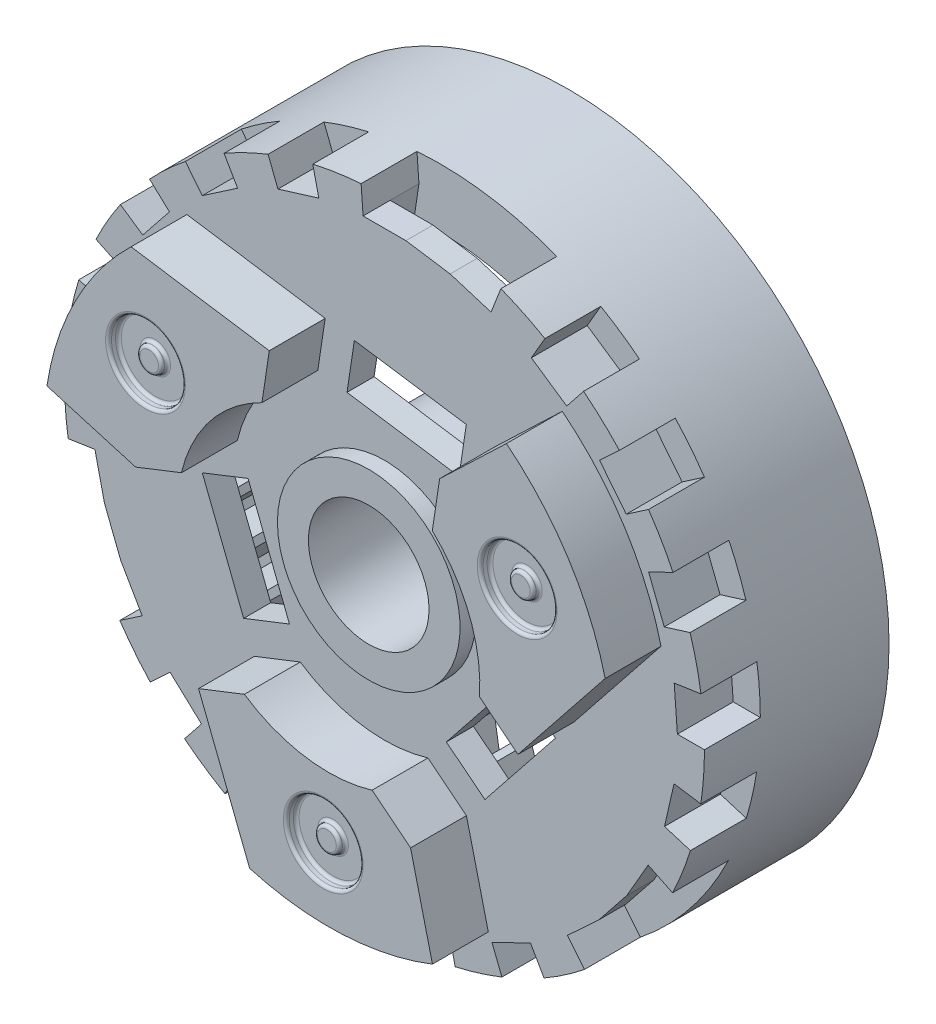
SolidWorks part; units mm, degrees
ref_plane "Front Plane" through (0, 0, 0) normal (0, 0, 1) x (1, 0, 0)
ref_plane "Top Plane" through (0, 0, 0) normal (0, 1, 0) x (1, 0, 0)
ref_plane "Right Plane" through (0, 0, 0) normal (1, 0, 0) x (0, 0, -1)
sketch "Sketch1" plane through (0, 0, 0) normal (0, 0, 1) x (1, 0, 0)
  circle A0 centre (0, 0) radius 13
  circle A1 centre (0, 0) radius 10.6
  dimension "D1" = 26
  dimension "D2" = 2.4
extrude "Boss-Extrude1" add sketch "Sketch1" along normal blind 7.5 contours A0 A1 | A1 region at (-12.6323, 0, 0) region at (0, 0, 0)
extrude "Cut-Extrude1" cut sketch "Sketch1<3>" along normal blind 6.4 contours A1
sketch "Sketch1<3>" plane through (0, 0, 0) normal (0, 0, 1) x (1, 0, 0) same geometry as "Sketch1"
sketch "Sketch2" plane through (0, 0, 0) normal (0, 0, -1) x (-1, 0, 0)
  line L0 (1.5404, 10.7139) -> (2.2569, 11.7861)
  line L1 (0, 10.8241) -> (0.5566, 11.9874)
  line L2 (0.5566, 11.9874) -> (0.8558, 11.966)
  line L3 (0.8558, 11.966) -> (1.2412, 10.7353)
  line L4 (1.2412, 10.7353) -> (1.5404, 10.7139)
  line L5 (0, 10.8241) -> (1.2412, 10.7353) construction
  line L6 (0.7062, 11.9767) -> (0.6206, 10.7797) construction
  line L7 (2.2569, 11.7861) -> (2.55, 11.7224)
  line L8 (2.55, 11.7224) -> (2.7564, 10.4494)
  line L9 (2.7564, 10.4494) -> (3.0495, 10.3857)
  line L10 (1.5404, 10.7139) -> (2.7564, 10.4494) construction
  line L11 (2.4035, 11.7543) -> (2.1484, 10.5817) construction
  line L12 (3.0495, 10.3857) -> (3.9113, 11.345)
  line L13 (3.9113, 11.345) -> (4.1924, 11.2402)
  line L14 (4.1924, 11.2402) -> (4.2154, 9.9508)
  line L15 (4.2154, 9.9508) -> (4.4965, 9.846)
  line L16 (3.0495, 10.3857) -> (4.2154, 9.9508) construction
  line L17 (4.0518, 11.2926) -> (3.6325, 10.1682) construction
  line L18 (4.4965, 9.846) -> (5.486, 10.6729)
  line L19 (5.486, 10.6729) -> (5.7493, 10.5291)
  line L20 (5.7493, 10.5291) -> (5.5887, 9.2496)
  line L21 (5.5887, 9.2496) -> (5.852, 9.1058)
  line L22 (4.4965, 9.846) -> (5.5887, 9.2496) construction
  line L23 (5.6177, 10.601) -> (5.0426, 9.5478) construction
  line L24 (5.852, 9.1058) -> (6.9491, 9.7835)
  line L25 (6.9491, 9.7835) -> (7.1893, 9.6037)
  line L26 (7.1893, 9.6037) -> (6.8481, 8.3601)
  line L27 (6.8481, 8.3601) -> (7.0883, 8.1803)
  line L28 (5.852, 9.1058) -> (6.8481, 8.3601) construction
  line L29 (7.0692, 9.6936) -> (6.35, 8.733) construction
  line L30 (7.0883, 8.1803) -> (8.2707, 8.695)
  line L31 (8.2707, 8.695) -> (8.4828, 8.4828)
  line L32 (8.4828, 8.4828) -> (7.9682, 7.3004)
  line L33 (7.9682, 7.3004) -> (8.1803, 7.0883)
  line L34 (7.0883, 8.1803) -> (7.9682, 7.3004) construction
  line L35 (8.3768, 8.5889) -> (7.5282, 7.7404) construction
  line L36 (8.1803, 7.0883) -> (9.4239, 7.4294)
  line L37 (9.4239, 7.4294) -> (9.6037, 7.1893)
  line L38 (9.6037, 7.1893) -> (8.926, 6.0921)
  line L39 (8.926, 6.0921) -> (9.1058, 5.852)
  line L40 (8.1803, 7.0883) -> (8.926, 6.0921) construction
  line L41 (9.5138, 7.3093) -> (8.5532, 6.5902) construction
  line L42 (9.1058, 5.852) -> (10.3853, 6.0126)
  line L43 (10.3853, 6.0126) -> (10.5291, 5.7493)
  line L44 (10.5291, 5.7493) -> (9.7022, 4.7598)
  line L45 (9.7022, 4.7598) -> (9.846, 4.4965)
  line L46 (9.1058, 5.852) -> (9.7022, 4.7598) construction
  line L47 (10.4572, 5.881) -> (9.404, 5.3059) construction
  line L48 (9.846, 4.4965) -> (11.1353, 4.4734)
  line L49 (11.1353, 4.4734) -> (11.2402, 4.1924)
  line L50 (11.2402, 4.1924) -> (10.2808, 3.3306)
  line L51 (10.2808, 3.3306) -> (10.3857, 3.0495)
  line L52 (9.846, 4.4965) -> (10.2808, 3.3306) construction
  line L53 (11.1877, 4.3329) -> (10.0634, 3.9135) construction
  line L54 (10.3857, 3.0495) -> (11.6586, 2.8432)
  line L55 (11.6586, 2.8432) -> (11.7224, 2.55)
  line L56 (11.7224, 2.55) -> (10.6502, 1.8336)
  line L57 (10.6502, 1.8336) -> (10.7139, 1.5404)
  line L58 (10.3857, 3.0495) -> (10.6502, 1.8336) construction
  line L59 (11.6905, 2.6966) -> (10.5179, 2.4415) construction
  line L60 (10.7139, 1.5404) -> (11.9446, 1.1551)
  line L61 (11.9446, 1.1551) -> (11.966, 0.8558)
  line L62 (11.966, 0.8558) -> (10.8027, 0.2992)
  line L63 (10.8027, 0.2992) -> (10.8241, 0)
  line L64 (10.7139, 1.5404) -> (10.8027, 0.2992) construction
  line L65 (11.9553, 1.0054) -> (10.7583, 0.9198) construction
  line L66 (10.8241, 0) -> (11.9874, -0.5566)
  line L67 (11.9874, -0.5566) -> (11.966, -0.8558)
  line L68 (11.966, -0.8558) -> (10.7353, -1.2412)
  line L69 (10.7353, -1.2412) -> (10.7139, -1.5404)
  line L70 (10.8241, 0) -> (10.7353, -1.2412) construction
  line L71 (11.9767, -0.7062) -> (10.7797, -0.6206) construction
  line L72 (10.7139, -1.5404) -> (11.7861, -2.2569)
  line L73 (11.7861, -2.2569) -> (11.7224, -2.55)
  line L74 (11.7224, -2.55) -> (10.4494, -2.7564)
  line L75 (10.4494, -2.7564) -> (10.3857, -3.0495)
  line L76 (10.7139, -1.5404) -> (10.4494, -2.7564) construction
  line L77 (11.7543, -2.4035) -> (10.5817, -2.1484) construction
  line L78 (10.3857, -3.0495) -> (11.345, -3.9113)
  line L79 (11.345, -3.9113) -> (11.2402, -4.1924)
  line L80 (11.2402, -4.1924) -> (9.9508, -4.2154)
  line L81 (9.9508, -4.2154) -> (9.846, -4.4965)
  line L82 (10.3857, -3.0495) -> (9.9508, -4.2154) construction
  line L83 (11.2926, -4.0518) -> (10.1682, -3.6325) construction
  line L84 (9.846, -4.4965) -> (10.6729, -5.486)
  line L85 (10.6729, -5.486) -> (10.5291, -5.7493)
  line L86 (10.5291, -5.7493) -> (9.2496, -5.5887)
  line L87 (9.2496, -5.5887) -> (9.1058, -5.852)
  line L88 (9.846, -4.4965) -> (9.2496, -5.5887) construction
  line L89 (10.601, -5.6177) -> (9.5478, -5.0426) construction
  line L90 (9.1058, -5.852) -> (9.7835, -6.9491)
  line L91 (9.7835, -6.9491) -> (9.6037, -7.1893)
  line L92 (9.6037, -7.1893) -> (8.3601, -6.8481)
  line L93 (8.3601, -6.8481) -> (8.1803, -7.0883)
  line L94 (9.1058, -5.852) -> (8.3601, -6.8481) construction
  line L95 (9.6936, -7.0692) -> (8.733, -6.35) construction
  line L96 (8.1803, -7.0883) -> (8.695, -8.2707)
  line L97 (8.695, -8.2707) -> (8.4828, -8.4828)
  line L98 (8.4828, -8.4828) -> (7.3004, -7.9682)
  line L99 (7.3004, -7.9682) -> (7.0883, -8.1803)
  line L100 (8.1803, -7.0883) -> (7.3004, -7.9682) construction
  line L101 (8.5889, -8.3768) -> (7.7404, -7.5282) construction
  line L102 (7.0883, -8.1803) -> (7.4294, -9.4239)
  line L103 (7.4294, -9.4239) -> (7.1893, -9.6037)
  line L104 (7.1893, -9.6037) -> (6.0921, -8.926)
  line L105 (6.0921, -8.926) -> (5.852, -9.1058)
  line L106 (7.0883, -8.1803) -> (6.0921, -8.926) construction
  line L107 (7.3093, -9.5138) -> (6.5902, -8.5532) construction
  line L108 (5.852, -9.1058) -> (6.0126, -10.3853)
  line L109 (6.0126, -10.3853) -> (5.7493, -10.5291)
  line L110 (5.7493, -10.5291) -> (4.7598, -9.7022)
  line L111 (4.7598, -9.7022) -> (4.4965, -9.846)
  line L112 (5.852, -9.1058) -> (4.7598, -9.7022) construction
  line L113 (5.881, -10.4572) -> (5.3059, -9.404) construction
  line L114 (4.4965, -9.846) -> (4.4734, -11.1353)
  line L115 (4.4734, -11.1353) -> (4.1924, -11.2402)
  line L116 (4.1924, -11.2402) -> (3.3306, -10.2808)
  line L117 (3.3306, -10.2808) -> (3.0495, -10.3857)
  line L118 (4.4965, -9.846) -> (3.3306, -10.2808) construction
  line L119 (4.3329, -11.1877) -> (3.9135, -10.0634) construction
  line L120 (3.0495, -10.3857) -> (2.8432, -11.6586)
  line L121 (2.8432, -11.6586) -> (2.55, -11.7224)
  line L122 (2.55, -11.7224) -> (1.8336, -10.6502)
  line L123 (1.8336, -10.6502) -> (1.5404, -10.7139)
  line L124 (3.0495, -10.3857) -> (1.8336, -10.6502) construction
  line L125 (2.6966, -11.6905) -> (2.4415, -10.5179) construction
  line L126 (1.5404, -10.7139) -> (1.1551, -11.9446)
  line L127 (1.1551, -11.9446) -> (0.8558, -11.966)
  line L128 (0.8558, -11.966) -> (0.2992, -10.8027)
  line L129 (0.2992, -10.8027) -> (0, -10.8241)
  line L130 (1.5404, -10.7139) -> (0.2992, -10.8027) construction
  line L131 (1.0054, -11.9553) -> (0.9198, -10.7583) construction
  line L132 (0, -10.8241) -> (-0.5566, -11.9874)
  line L133 (-0.5566, -11.9874) -> (-0.8558, -11.966)
  line L134 (-0.8558, -11.966) -> (-1.2412, -10.7353)
  line L135 (-1.2412, -10.7353) -> (-1.5404, -10.7139)
  line L136 (0, -10.8241) -> (-1.2412, -10.7353) construction
  line L137 (-0.7062, -11.9767) -> (-0.6206, -10.7797) construction
  line L138 (-1.5404, -10.7139) -> (-2.2569, -11.7861)
  line L139 (-2.2569, -11.7861) -> (-2.55, -11.7224)
  line L140 (-2.55, -11.7224) -> (-2.7564, -10.4494)
  line L141 (-2.7564, -10.4494) -> (-3.0495, -10.3857)
  line L142 (-1.5404, -10.7139) -> (-2.7564, -10.4494) construction
  line L143 (-2.4035, -11.7543) -> (-2.1484, -10.5817) construction
  line L144 (-3.0495, -10.3857) -> (-3.9113, -11.345)
  line L145 (-3.9113, -11.345) -> (-4.1924, -11.2402)
  line L146 (-4.1924, -11.2402) -> (-4.2154, -9.9508)
  line L147 (-4.2154, -9.9508) -> (-4.4965, -9.846)
  line L148 (-3.0495, -10.3857) -> (-4.2154, -9.9508) construction
  line L149 (-4.0518, -11.2926) -> (-3.6325, -10.1682) construction
  line L150 (-4.4965, -9.846) -> (-5.486, -10.6729)
  line L151 (-5.486, -10.6729) -> (-5.7493, -10.5291)
  line L152 (-5.7493, -10.5291) -> (-5.5887, -9.2496)
  line L153 (-5.5887, -9.2496) -> (-5.852, -9.1058)
  line L154 (-4.4965, -9.846) -> (-5.5887, -9.2496) construction
  line L155 (-5.6177, -10.601) -> (-5.0426, -9.5478) construction
  line L156 (-5.852, -9.1058) -> (-6.9491, -9.7835)
  line L157 (-6.9491, -9.7835) -> (-7.1893, -9.6037)
  line L158 (-7.1893, -9.6037) -> (-6.8481, -8.3601)
  line L159 (-6.8481, -8.3601) -> (-7.0883, -8.1803)
  line L160 (-5.852, -9.1058) -> (-6.8481, -8.3601) construction
  line L161 (-7.0692, -9.6936) -> (-6.35, -8.733) construction
  line L162 (-7.0883, -8.1803) -> (-8.2707, -8.695)
  line L163 (-8.2707, -8.695) -> (-8.4828, -8.4828)
  line L164 (-8.4828, -8.4828) -> (-7.9682, -7.3004)
  line L165 (-7.9682, -7.3004) -> (-8.1803, -7.0883)
  line L166 (-7.0883, -8.1803) -> (-7.9682, -7.3004) construction
  line L167 (-8.3768, -8.5889) -> (-7.5282, -7.7404) construction
  line L168 (-8.1803, -7.0883) -> (-9.4239, -7.4294)
  line L169 (-9.4239, -7.4294) -> (-9.6037, -7.1893)
  line L170 (-9.6037, -7.1893) -> (-8.926, -6.0921)
  line L171 (-8.926, -6.0921) -> (-9.1058, -5.852)
  line L172 (-8.1803, -7.0883) -> (-8.926, -6.0921) construction
  line L173 (-9.5138, -7.3093) -> (-8.5532, -6.5902) construction
  line L174 (-9.1058, -5.852) -> (-10.3853, -6.0126)
  line L175 (-10.3853, -6.0126) -> (-10.5291, -5.7493)
  line L176 (-10.5291, -5.7493) -> (-9.7022, -4.7598)
  line L177 (-9.7022, -4.7598) -> (-9.846, -4.4965)
  line L178 (-9.1058, -5.852) -> (-9.7022, -4.7598) construction
  line L179 (-10.4572, -5.881) -> (-9.404, -5.3059) construction
  line L180 (-9.846, -4.4965) -> (-11.1353, -4.4734)
  line L181 (-11.1353, -4.4734) -> (-11.2402, -4.1924)
  line L182 (-11.2402, -4.1924) -> (-10.2808, -3.3306)
  line L183 (-10.2808, -3.3306) -> (-10.3857, -3.0495)
  line L184 (-9.846, -4.4965) -> (-10.2808, -3.3306) construction
  line L185 (-11.1877, -4.3329) -> (-10.0634, -3.9135) construction
  line L186 (-10.3857, -3.0495) -> (-11.6586, -2.8432)
  line L187 (-11.6586, -2.8432) -> (-11.7224, -2.55)
  line L188 (-11.7224, -2.55) -> (-10.6502, -1.8336)
  line L189 (-10.6502, -1.8336) -> (-10.7139, -1.5404)
  line L190 (-10.3857, -3.0495) -> (-10.6502, -1.8336) construction
  line L191 (-11.6905, -2.6966) -> (-10.5179, -2.4415) construction
  line L192 (-10.7139, -1.5404) -> (-11.9446, -1.1551)
  line L193 (-11.9446, -1.1551) -> (-11.966, -0.8558)
  line L194 (-11.966, -0.8558) -> (-10.8027, -0.2992)
  line L195 (-10.8027, -0.2992) -> (-10.8241, 0)
  line L196 (-10.7139, -1.5404) -> (-10.8027, -0.2992) construction
  line L197 (-11.9553, -1.0054) -> (-10.7583, -0.9198) construction
  line L198 (-10.8241, 0) -> (-11.9874, 0.5566)
  line L199 (-11.9874, 0.5566) -> (-11.966, 0.8558)
  line L200 (-11.966, 0.8558) -> (-10.7353, 1.2412)
  line L201 (-10.7353, 1.2412) -> (-10.7139, 1.5404)
  line L202 (-10.8241, 0) -> (-10.7353, 1.2412) construction
  line L203 (-11.9767, 0.7062) -> (-10.7797, 0.6206) construction
  line L204 (-10.7139, 1.5404) -> (-11.7861, 2.2569)
  line L205 (-11.7861, 2.2569) -> (-11.7224, 2.55)
  line L206 (-11.7224, 2.55) -> (-10.4494, 2.7564)
  line L207 (-10.4494, 2.7564) -> (-10.3857, 3.0495)
  line L208 (-10.7139, 1.5404) -> (-10.4494, 2.7564) construction
  line L209 (-11.7543, 2.4035) -> (-10.5817, 2.1484) construction
  line L210 (-10.3857, 3.0495) -> (-11.345, 3.9113)
  line L211 (-11.345, 3.9113) -> (-11.2402, 4.1924)
  line L212 (-11.2402, 4.1924) -> (-9.9508, 4.2154)
  line L213 (-9.9508, 4.2154) -> (-9.846, 4.4965)
  line L214 (-10.3857, 3.0495) -> (-9.9508, 4.2154) construction
  line L215 (-11.2926, 4.0518) -> (-10.1682, 3.6325) construction
  line L216 (-9.846, 4.4965) -> (-10.6729, 5.486)
  line L217 (-10.6729, 5.486) -> (-10.5291, 5.7493)
  line L218 (-10.5291, 5.7493) -> (-9.2496, 5.5887)
  line L219 (-9.2496, 5.5887) -> (-9.1058, 5.852)
  line L220 (-9.846, 4.4965) -> (-9.2496, 5.5887) construction
  line L221 (-10.601, 5.6177) -> (-9.5478, 5.0426) construction
  line L222 (-9.1058, 5.852) -> (-9.7835, 6.9491)
  line L223 (-9.7835, 6.9491) -> (-9.6037, 7.1893)
  line L224 (-9.6037, 7.1893) -> (-8.3601, 6.8481)
  line L225 (-8.3601, 6.8481) -> (-8.1803, 7.0883)
  line L226 (-9.1058, 5.852) -> (-8.3601, 6.8481) construction
  line L227 (-9.6936, 7.0692) -> (-8.733, 6.35) construction
  line L228 (-8.1803, 7.0883) -> (-8.695, 8.2707)
  line L229 (-8.695, 8.2707) -> (-8.4828, 8.4828)
  line L230 (-8.4828, 8.4828) -> (-7.3004, 7.9682)
  line L231 (-7.3004, 7.9682) -> (-7.0883, 8.1803)
  line L232 (-8.1803, 7.0883) -> (-7.3004, 7.9682) construction
  line L233 (-8.5889, 8.3768) -> (-7.7404, 7.5282) construction
  line L234 (-7.0883, 8.1803) -> (-7.4294, 9.4239)
  line L235 (-7.4294, 9.4239) -> (-7.1893, 9.6037)
  line L236 (-7.1893, 9.6037) -> (-6.0921, 8.926)
  line L237 (-6.0921, 8.926) -> (-5.852, 9.1058)
  line L238 (-7.0883, 8.1803) -> (-6.0921, 8.926) construction
  line L239 (-7.3093, 9.5138) -> (-6.5902, 8.5532) construction
  line L240 (-5.852, 9.1058) -> (-6.0126, 10.3853)
  line L241 (-6.0126, 10.3853) -> (-5.7493, 10.5291)
  line L242 (-5.7493, 10.5291) -> (-4.7598, 9.7022)
  line L243 (-4.7598, 9.7022) -> (-4.4965, 9.846)
  line L244 (-5.852, 9.1058) -> (-4.7598, 9.7022) construction
  line L245 (-5.881, 10.4572) -> (-5.3059, 9.404) construction
  line L246 (-4.4965, 9.846) -> (-4.4734, 11.1353)
  line L247 (-4.4734, 11.1353) -> (-4.1924, 11.2402)
  line L248 (-4.1924, 11.2402) -> (-3.3306, 10.2808)
  line L249 (-3.3306, 10.2808) -> (-3.0495, 10.3857)
  line L250 (-4.4965, 9.846) -> (-3.3306, 10.2808) construction
  line L251 (-4.3329, 11.1877) -> (-3.9135, 10.0634) construction
  line L252 (-3.0495, 10.3857) -> (-2.8432, 11.6586)
  line L253 (-2.8432, 11.6586) -> (-2.55, 11.7224)
  line L254 (-2.55, 11.7224) -> (-1.8336, 10.6502)
  line L255 (-1.8336, 10.6502) -> (-1.5404, 10.7139)
  line L256 (-3.0495, 10.3857) -> (-1.8336, 10.6502) construction
  line L257 (-2.6966, 11.6905) -> (-2.4415, 10.5179) construction
  line L258 (-1.5404, 10.7139) -> (-1.1551, 11.9446)
  line L259 (-1.1551, 11.9446) -> (-0.8558, 11.966)
  line L260 (-0.8558, 11.966) -> (-0.2992, 10.8027)
  line L261 (-0.2992, 10.8027) -> (0, 10.8241)
  line L262 (-1.5404, 10.7139) -> (-0.2992, 10.8027) construction
  line L263 (-1.0054, 11.9553) -> (-0.9198, 10.7583) construction
  line L264 (0.5566, 11.9874) -> (0.6279, 12.9848) construction
  circle A0 centre (0, 0) radius 13 construction
  point P313 (0, 0)
  dimension "D1" = 1
  dimension "D2" = 0.3
  dimension "D4" = 1.2
  dimension "D6" = 44
extrude "Cut-Extrude2" cut sketch "Sketch2" against normal blind 4.35
sketch "Sketch3" plane through (0, 0, 6.4) normal (0, 0, -1) x (-1, 0, 0)
  circle A0 centre (0, 0) radius 2.45
  circle A1 centre (0, 0) radius 3.71
  dimension "D1" = 4.9
  dimension "D2" = 7.42
extrude "Boss-Extrude2" add sketch "Sketch3" along normal offset from surface (6.9 mm away) 0.5 up to face at (0, 0, 0) offset beyond the face yes
extrude "Cut-Extrude3" cut sketch "Sketch3<2>" against normal through all contours A0
sketch "Sketch3<2>" plane through (0, 0, 6.4) normal (0, 0, -1) x (-1, 0, 0) same geometry as "Sketch3"
extrude "Boss-Extrude3" add sketch "Sketch3<3>" against normal blind 0.64 from surface starting at face at (-2.45, 0, 7.5)
sketch "Sketch3<3>" plane through (0, 0, 6.4) normal (0, 0, -1) x (-1, 0, 0) same geometry as "Sketch3"
sketch "Sketch4" plane through (0, 0, 7.5) normal (0, 0, 1) x (1, 0, 0)
  line L0 (2.9138, 12.6693) -> (2.6672, 11.5972)
  line L2 (-0.95, 12.9652) -> (-0.8696, 11.8682)
  line L3 (-0.8696, 11.8682) -> (0.8696, 11.8682)
  line L4 (0.95, 12.9652) -> (0.8696, 11.8682)
  line L5 (2.6672, 11.5972) -> (4.3292, 11.0846)
  line L6 (4.7294, 12.1092) -> (4.3292, 11.0846)
  line L7 (6.5187, 11.2475) -> (5.9671, 10.2958)
  line L8 (5.9671, 10.2958) -> (7.4041, 9.3161)
  line L9 (8.0885, 10.1772) -> (7.4041, 9.3161)
  line L10 (9.5443, 8.8264) -> (8.7367, 8.0796)
  line L11 (8.7367, 8.0796) -> (9.8211, 6.7198)
  line L12 (10.7289, 7.341) -> (9.8211, 6.7198)
  line L13 (11.7219, 5.6211) -> (10.7301, 5.1454)
  line L14 (10.7301, 5.1454) -> (11.3655, 3.5264)
  line L15 (12.4161, 3.8524) -> (11.3655, 3.5264)
  line L16 (12.858, 1.9162) -> (11.77, 1.7541)
  line L17 (11.77, 1.7541) -> (11.9, 0.0197)
  line L18 (13, 0.0216) -> (11.9, 0.0197)
  line L19 (12.8516, -1.9589) -> (11.7641, -1.7931)
  line L20 (11.7641, -1.7931) -> (11.3771, -3.4887)
  line L21 (12.4288, -3.8112) -> (11.3771, -3.4887)
  line L22 (11.7032, -5.6599) -> (10.713, -5.181)
  line L23 (10.713, -5.181) -> (9.8433, -6.6872)
  line L24 (10.7532, -7.3053) -> (9.8433, -6.6872)
  line L25 (9.515, -8.858) -> (8.7099, -8.1085)
  line L26 (8.7099, -8.1085) -> (7.4349, -9.2915)
  line L27 (8.1222, -10.1504) -> (7.4349, -9.2915)
  line L28 (6.4813, -11.2691) -> (5.9329, -10.3156)
  line L29 (5.9329, -10.3156) -> (4.3659, -11.0702)
  line L30 (4.7695, -12.0935) -> (4.3659, -11.0702)
  line L31 (2.8718, -12.6788) -> (2.6288, -11.606)
  line L32 (2.6288, -11.606) -> (0.909, -11.8652)
  line L33 (0.993, -12.962) -> (0.909, -11.8652)
  line L34 (-0.993, -12.962) -> (-0.909, -11.8652)
  line L35 (-0.909, -11.8652) -> (-2.6288, -11.606)
  line L36 (-2.8718, -12.6788) -> (-2.6288, -11.606)
  line L37 (-4.7695, -12.0935) -> (-4.3659, -11.0702)
  line L38 (-4.3659, -11.0702) -> (-5.9329, -10.3156)
  line L39 (-6.4813, -11.2691) -> (-5.9329, -10.3156)
  line L40 (-8.1222, -10.1504) -> (-7.4349, -9.2915)
  line L41 (-7.4349, -9.2915) -> (-8.7099, -8.1085)
  line L42 (-9.515, -8.858) -> (-8.7099, -8.1085)
  line L43 (-10.7532, -7.3053) -> (-9.8433, -6.6872)
  line L44 (-9.8433, -6.6872) -> (-10.713, -5.181)
  line L45 (-11.7032, -5.6599) -> (-10.713, -5.181)
  line L46 (-12.4288, -3.8112) -> (-11.3771, -3.4887)
  line L47 (-11.3771, -3.4887) -> (-11.7641, -1.7931)
  line L48 (-12.8516, -1.9589) -> (-11.7641, -1.7931)
  line L49 (-13, 0.0216) -> (-11.9, 0.0197)
  line L50 (-11.9, 0.0197) -> (-11.77, 1.7541)
  line L51 (-12.858, 1.9162) -> (-11.77, 1.7541)
  line L52 (-12.4161, 3.8524) -> (-11.3655, 3.5264)
  line L53 (-11.3655, 3.5264) -> (-10.7301, 5.1454)
  line L54 (-11.7219, 5.6211) -> (-10.7301, 5.1454)
  line L55 (-10.7289, 7.341) -> (-9.8211, 6.7198)
  line L56 (-9.8211, 6.7198) -> (-8.7367, 8.0796)
  line L57 (-9.5443, 8.8264) -> (-8.7367, 8.0796)
  line L58 (-8.0885, 10.1772) -> (-7.4041, 9.3161)
  line L59 (-7.4041, 9.3161) -> (-5.9671, 10.2958)
  line L60 (-6.5187, 11.2475) -> (-5.9671, 10.2958)
  line L61 (-4.7294, 12.1092) -> (-4.3292, 11.0846)
  line L62 (-4.3292, 11.0846) -> (-2.6672, 11.5972)
  line L63 (-2.9138, 12.6693) -> (-2.6672, 11.5972)
  line L64 (-0.95, 12.9652) -> (-0.4583, 13.0013) construction
  line L65 (0.95, 12.9652) -> (2.1086, 12.8803) construction
  line L66 (0.95, 12.9652) -> (2.9138, 12.6693)
  line L67 (4.7294, 12.1092) -> (6.5187, 11.2475)
  line L68 (8.0885, 10.1772) -> (9.5443, 8.8264)
  line L69 (10.7289, 7.341) -> (11.7219, 5.6211)
  line L70 (12.4161, 3.8524) -> (12.858, 1.9162)
  line L71 (13, 0.0216) -> (12.8516, -1.9589)
  line L72 (12.4288, -3.8112) -> (11.7032, -5.6599)
  line L73 (10.7532, -7.3053) -> (9.515, -8.858)
  line L74 (8.1222, -10.1504) -> (6.4813, -11.2691)
  line L75 (4.7695, -12.0935) -> (2.8718, -12.6788)
  line L76 (0.993, -12.962) -> (-0.993, -12.962)
  line L77 (-2.8718, -12.6788) -> (-4.7695, -12.0935)
  line L78 (-6.4813, -11.2691) -> (-8.1222, -10.1504)
  line L79 (-9.515, -8.858) -> (-10.7532, -7.3053)
  line L80 (-11.7032, -5.6599) -> (-12.4288, -3.8112)
  line L81 (-12.8516, -1.9589) -> (-13, 0.0216)
  line L82 (-12.858, 1.9162) -> (-12.4161, 3.8524)
  line L83 (-11.7219, 5.6211) -> (-10.7289, 7.341)
  line L84 (-9.5443, 8.8264) -> (-8.0885, 10.1772)
  line L85 (-6.5187, 11.2475) -> (-4.7294, 12.1092)
  line L86 (-2.9138, 12.6693) -> (-0.95, 12.9652)
  circle A0 centre (0, 0) radius 13 construction
  circle A1 centre (0, 0) radius 15.8239
  point P89 (0, 0)
  point P132 (0, 0)
  circle M88 centre (0, 0) radius 13
  dimension "D1" = 1.1
  dimension "D2" = 1.9
  dimension "D4" = 21
  dimension "D3" = 21
extrude "Cut-Extrude4" cut sketch "Sketch4" against normal blind 2.27 contours L63 L61 L62 M88 | L6 L0 L5 M88 | L9 L7 L8 M88 | L12 L10 L11 M88 | L18 L16 L17 M88 | L21 L19 L20 M88 | L27 L25 L26 M88 | L30 L28 L29 M88 | L33 L31 L32 M88 | L36 L34 L35 M88 | L39 L37 L38 M88 | L42 L40 L41 M88 | L48 L46 L47 M88 | L51 L49 L50 M88 | L57 L55 L56 M88 | L60 L58 L59 M88 | A1 M88 | L15 L13 L14 M88 | L54 L52 L53 M88 | L4 L2 L3 M88 | L24 L22 L23 M88 | L45 L43 L44 M88 region at (3.6658, 11.8842, 7.5) region at (0, 12.4368, 7.5) region at (7.0059, 10.2757, 7.5) region at (-3.6658, 11.8842, 7.5) region at (9.7234, 7.7542, 7.5) region at (-7.0059, 10.2757, 7.5) region at (11.577, 4.5437, 7.5) region at (-9.7234, 7.7542, 7.5) region at (12.402, 0.9294, 7.5) region at (-11.577, 4.5437, 7.5) region at (12.1249, -2.7674, 7.5) region at (-12.402, 0.9294, 7.5) region at (10.7705, -6.2184, 7.5) region at (-12.1249, -2.7674, 7.5) region at (8.4591, -9.1168, 7.5) region at (-10.7705, -6.2184, 7.5) region at (5.3961, -11.2051, 7.5) region at (-8.4591, -9.1168, 7.5) region at (1.8536, -12.2978, 7.5) region at (-5.3961, -11.2051, 7.5) region at (-1.8536, -12.2978, 7.5) region at (-15.3763, 0, 7.5)
sketch "Sketch5" plane through (0, 0, 7.5) normal (0, 0, 1) x (1, 0, 0)
  line L0 (2.9138, 12.6693) -> (2.6672, 11.5972) construction
  line L1 (0.95, 12.9652) -> (0.8696, 11.8682) construction
  line L2 (2.9138, 12.6693) -> (2.6672, 11.5972)
  line L3 (0.95, 12.9652) -> (0.8696, 11.8682)
  line L4 (0.8696, 11.8682) -> (2.6672, 11.5972)
  arc A0 (2.9138, 12.6693) -> (0.95, 12.9652) centre (0, 0) ccw construction
  arc A1 (2.9138, 12.6693) -> (0.95, 12.9652) centre (0, 0) ccw
extrude "Cut-Extrude5" cut sketch "Sketch5" against normal up to surface (2.27 mm away) up to face at (3.6625, 11.8734, 5.23)
sketch "Sketch6" plane through (1.7684, 11.7327, 0) normal (0.149, 0.9888, 0) x (0.9888, -0.149, 0)
  line L0 (10.6, -6.4) -> (-10.6, -6.4) construction
  line L1 (2.6288, -6.4) -> (-2.6288, -6.4)
  line L2 (2.6288, -6.4) -> (2.6288, -5.23)
  line L3 (2.6288, -5.23) -> (-2.6288, -5.23)
  line L4 (-2.6288, -6.4) -> (-2.6288, -5.23)
  line L5 (10.6, -6.4) -> (-10.6, -6.4) construction
extrude "Cut-Extrude6" cut sketch "Sketch6" against normal blind 2.27
pattern_circular "CirPattern1" count 3 over 360 about axis through (0, 0, 6.4) along (0, 0, 1) of "Cut-Extrude6", "Cut-Extrude5"
sketch "Sketch7" plane through (0, 0, 7.5) normal (0, 0, 1) x (1, 0, 0)
  line L0 (-5.7224, -4.7167) -> (-7.4029, -0.4346)
  line L1 (-5.7224, -4.7167) -> (-3.8606, -3.986)
  line L2 (-7.4029, -0.4346) -> (-5.5412, 0.296)
  line L3 (-3.8606, -3.986) -> (-5.5412, 0.296)
  line L4 (-3.4535, -1.3554) -> (-4.8653, 2.2417) construction
  line L5 (-3.4535, -1.3554) -> (0, 0) construction
  line L6 (-3.4535, -1.3554) -> (-4.7009, -1.845) construction
  line L7 (-11.045, -4.3349) -> (-6.5627, -2.5757) construction
  line L8 (-10.713, -5.181) -> (-11.3771, -3.4887) construction
  circle A0 centre (0, 0) radius 3.71 construction
  circle A3 centre (0, 0) radius 2.45 construction
  dimension "D1" = 4.6
  dimension "D2" = 2
  dimension "D3" = 2.6
extrude "Cut-Extrude7" cut sketch "Sketch7" against normal through all
pattern_circular "CirPattern2" count 3 over 360 about axis through (0, 0, 8.14) along (0, 0, 1) of "Cut-Extrude7"
sketch "Sketch8" plane through (0, 0, 7.5) normal (0, 0, 1) x (1, 0, 0)
  line L0 (-7.8414, 0.6824) -> (-5.9796, 1.4131)
  line L1 (-2.7082, 5.5152) -> (-2.4102, 7.4929)
  line L2 (-5.5412, 0.296) -> (-7.4029, -0.4346) construction
  line L3 (-1.2236, 7.3141) -> (-1.5216, 5.3364) construction
  line L4 (-5.5412, 0.296) -> (-5.9796, 1.4131) construction
  line L5 (-2.7082, 5.5152) -> (-1.5216, 5.3364) construction
  line L6 (-1.5216, 5.3364) -> (3.027, 4.6508) construction
  line L7 (-3.8606, -3.986) -> (-5.5412, 0.296) construction
  line L8 (-2.4102, 7.4929) -> (-8.0265, 8.3394)
  line L9 (3.3251, 6.6285) -> (-1.2236, 7.3141) construction
  line L10 (-7.8414, 0.6824) -> (-11.4436, 1.736)
  arc A0 (-2.7082, 5.5152) -> (-5.9796, 1.4131) centre (0, 0) ccw
  arc A1 (-8.0265, 8.3394) -> (-11.4436, 1.736) centre (0, 0) ccw
  dimension "D1" = 1.2
extrude "Boss-Extrude4" add sketch "Sketch8" along normal blind 2.27
sketch "Sketch9" plane through (0, 0, 9.77) normal (0, 0, 1) x (1, 0, 0)
  line L0 (-9.6425, 1.2092) -> (-5.2183, 7.9162) construction
  line L1 (-11.4436, 1.736) -> (-7.8414, 0.6824) construction
  line L2 (-2.4102, 7.4929) -> (-8.0265, 8.3394) construction
  line L3 (-10.2797, 5.3196) -> (-4.8038, 3.8309) construction
  arc A0 (-8.0265, 8.3394) -> (-11.4436, 1.736) centre (0, 0) ccw construction
  arc A1 (-2.7082, 5.5152) -> (-5.9796, 1.4131) centre (0, 0) ccw construction
  circle A2 centre (-7.4403, 4.5477) radius 1.5
  circle A3 centre (-7.4403, 4.5477) radius 0.5
  dimension "D1" = 3
  dimension "D2" = 1
extrude "Cut-Extrude8" cut sketch "Sketch9" against normal blind 0.4 contours A2 A3 region at (-8.8979, 4.5477, 9.77)
extrude "Cut-Extrude9" cut sketch "Sketch9<3>" against normal blind 0.15 contours A3 region at (-7.4403, 4.5477, 9.77)
sketch "Sketch9<3>" plane through (0, 0, 9.77) normal (0, 0, 1) x (1, 0, 0) same geometry as "Sketch9"
fillet "Fillet1" radius 0.12 4 edges at (-5.9403, 4.5477, 9.77) (-5.9403, 4.5477, 9.37) (-6.9403, 4.5477, 9.37) (-6.9403, 4.5477, 9.62)
pattern_circular "CirPattern3" count 3 over 360 about axis through (0, 0, 8.14) along (0, 0, 1) of "Boss-Extrude4", "Cut-Extrude8", "Cut-Extrude9", "Fillet1"
